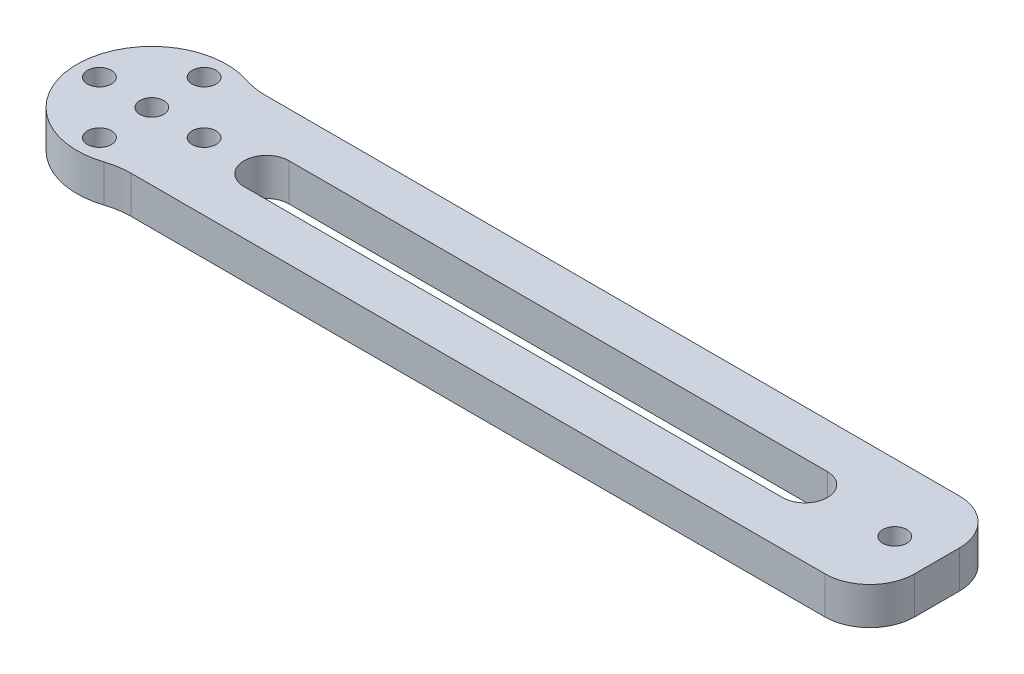
SolidWorks part; units mm, degrees
ref_plane "前视基准面" through (0, 0, 0) normal (0, 0, 1) x (1, 0, 0)
ref_plane "上视基准面" through (0, 0, 0) normal (0, 1, 0) x (1, 0, 0)
ref_plane "右视基准面" through (0, 0, 0) normal (1, 0, 0) x (0, 0, -1)
other "Configuration Table"
sketch "草图1" plane through (0, 0, 0) normal (0, 1, 0) x (1, 0, 0)
  line L0 (-9, 0) -> (0, 0) construction
  line L1 (0, 9) -> (99, 9)
  line L2 (105, 3) -> (105, -3)
  line L3 (99, -9) -> (0, -9)
  line L4 (0, 0) -> (99.34, 0) construction
  line L5 (15.34, 0) -> (87.34, 0) construction
  line L6 (15.34, 3) -> (87.34, 3)
  line L7 (15.34, -3) -> (87.34, -3)
  circle A0 centre (0, 0) radius 1.6
  circle A1 centre (0, 0) radius 9
  circle A2 centre (0, 0) radius 7 construction
  circle A3 centre (-7, 0) radius 1.6
  circle A4 centre (0, 7) radius 1.6
  circle A5 centre (7, 0) radius 1.6
  circle A6 centre (0, -7) radius 1.6
  circle A7 centre (99.34, 0) radius 1.6
  arc A8 (105, -3) -> (99, -9) centre (99, -3) cw
  arc A9 (99, 9) -> (105, 3) centre (99, 3) cw
  arc A10 (15.34, 3) -> (15.34, -3) centre (15.34, 0) ccw
  arc A11 (87.34, -3) -> (87.34, 3) centre (87.34, 0) ccw
  point P16 (0, 0)
  point P25 (105, 9)
  point P28 (51.34, 0)
  dimension "D1" = 3.2
  dimension "D2" = 18
  dimension "D3" = 14
  dimension "D4" = 3.2
  dimension "D7" = 3.2
  dimension "D10" = 6
  dimension "D12" = 3
  dimension "D6" = 105
  dimension "D8" = 9
  dimension "D9" = 5.66
  dimension "D11" = 72
  dimension "D13" = 12
  dimension "D5" = 4
extrude "凸台-拉伸1" add sketch "草图1" along normal blind 5 contours A9 L1 A1 L3 A8 L2 A11 L7 A10 L6 A7 | A1 A6 A5 A4 A3 A0 region at (49.5, 0, -7.9347) region at (6.184, 0, -6.184)
sketch "草图2" plane through (0, 0, 0) normal (0, -1, 0) x (1, 0, 0)
  circle A0 centre (99.34, 0) radius 4.2
  dimension "D1" = 8.4
extrude "切除-拉伸1" cut sketch "草图2" against normal blind 2.5
sketch "草图3" plane through (0, 5, 0) normal (0, 1, 0) x (1, 0, 0)
  circle A0 centre (0, 0) radius 9
  circle A1 centre (0, 0) radius 10
  dimension "D1" = 18
  dimension "D2" = 20
extrude "凸台-拉伸2" add sketch "草图3" against normal blind 5
fillet "圆角1" radius 10 2 edges at (4.3589, 2.5, 9) (4.3589, 2.5, -9)
